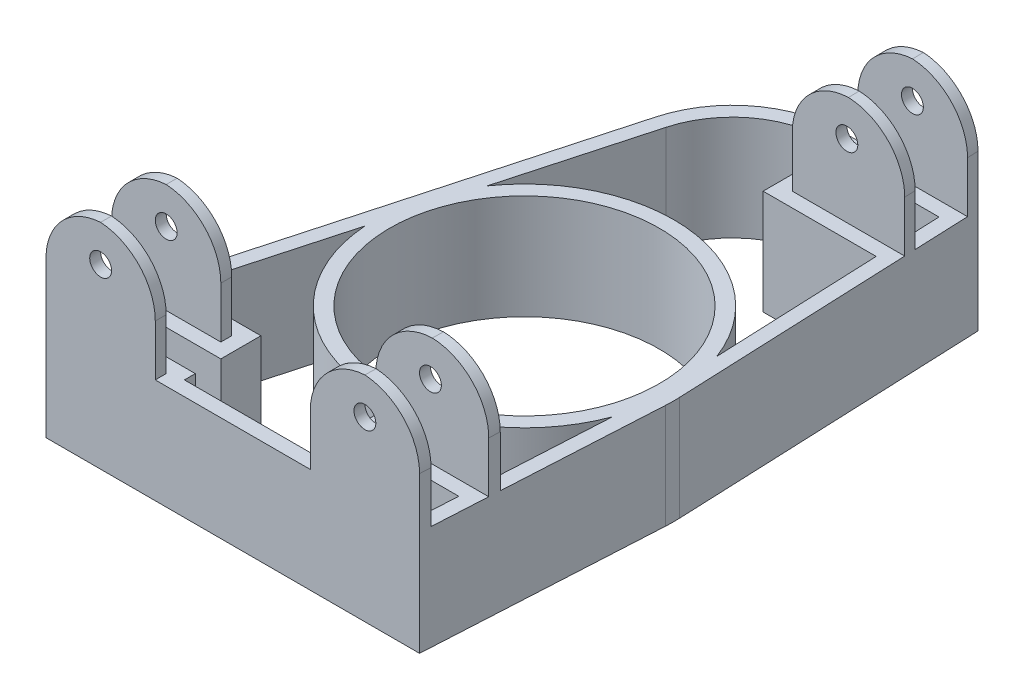
SolidWorks part; units mm, degrees
ref_plane "Front Plane" through (0, 0, 0) normal (0, 0, 1) x (1, 0, 0)
ref_plane "Top Plane" through (0, 0, 0) normal (0, 1, 0) x (1, 0, 0)
ref_plane "Right Plane" through (0, 0, 0) normal (1, 0, 0) x (0, 0, -1)
sketch "Sketch1" plane through (0, 0, 0) normal (0, 1, 0) x (1, 0, 0)
  line L0 (-80.1293, -86.7158) -> (50.1253, -86.7158)
  line L1 (54.7506, -2.9754) -> (50.1253, 108.0147)
  line L2 (50.1253, 108.0147) -> (2.5753, 108.0147)
  line L3 (-34.1543, 80.0411) -> (-72.7763, -60.0458)
  line L4 (50.1253, 108.0147) -> (50.1253, -86.7158) construction
  line L5 (50.1253, -86.7158) -> (54.7506, -2.9754)
  line L6 (-80.1293, -86.7158) -> (-80.1293, -60.0458)
  line L7 (-80.1293, -60.0458) -> (-72.7763, -60.0458)
  circle A0 centre (0, 0) radius 47
  circle A2 centre (0, 0) radius 120.65
  arc A3 (2.5753, 108.0147) -> (-34.1543, 80.0411) centre (2.5753, 69.9147) ccw
  point P10 (0, -47)
  point P11 (47, 0)
  point P16 (-47, 0)
  dimension "D2" = 94
  dimension "D3" = 7.62
  dimension "D4" = 8.89
  dimension "D5" = 26.67
  dimension "D1" = 241.3
  dimension "D6" = 38.1
extrude "Base" add sketch "Sketch1" along normal blind 36.5 contours L2 L3 L0 L1 A0 | L1 L4 A0 L5
sketch "Sketch2" plane through (0, 36.5, 0) normal (0, 1, 0) x (1, 0, 0)
  line L0 (50.1253, 108.0147) -> (50.2841, 104.2047)
  line L1 (54.7506, -2.9754) -> (50.1253, 108.0147) construction
  line L2 (50.2841, 104.2047) -> (12.0253, 104.2047)
  line L3 (12.0253, 104.2047) -> (12.0253, 108.0147)
  line L4 (50.1253, 108.0147) -> (2.5753, 108.0147) construction
  line L5 (12.0253, 108.0147) -> (50.1253, 108.0147)
  line L6 (12.0253, -82.9058) -> (50.3357, -82.9058)
  line L7 (50.3357, -82.9058) -> (50.1253, -86.7158)
  line L8 (-80.1293, -86.7158) -> (50.1253, -86.7158) construction
  line L9 (50.1253, -86.7158) -> (12.0253, -86.7158)
  line L10 (12.0253, -86.7158) -> (12.0253, -82.9058)
  line L11 (12.0253, 108.0147) -> (12.0253, -86.7158) construction
  line L12 (50.1253, -86.7158) -> (54.7506, -2.9754) construction
  line L13 (12.0253, 85.1547) -> (12.0253, 81.3447)
  line L14 (12.0253, 81.3447) -> (51.2367, 81.3447)
  line L15 (51.2367, 81.3447) -> (51.0779, 85.1547)
  line L16 (51.0779, 85.1547) -> (12.0253, 85.1547)
  line L17 (-80.1293, -86.7158) -> (-80.1293, -60.0458) construction
  line L18 (12.0253, -60.0458) -> (51.5984, -60.0458)
  line L19 (12.0253, -60.0458) -> (12.0253, -63.8558)
  line L20 (12.0253, -63.8558) -> (51.3879, -63.8558)
  line L21 (51.5984, -60.0458) -> (51.3879, -63.8558)
  line L22 (-42.0293, -60.0458) -> (-80.1293, -60.0458)
  line L23 (-42.0293, -60.0458) -> (-42.0293, -63.8558)
  line L24 (-42.0293, -63.8558) -> (-80.1293, -63.8558)
  line L25 (-80.1293, -60.0458) -> (-80.1293, -63.8558)
  line L26 (-42.0293, -86.7158) -> (-42.0293, -60.0458) construction
  line L27 (-80.1293, -82.9058) -> (-42.0293, -82.9058)
  line L28 (-80.1293, -82.9058) -> (-80.1293, -86.7158)
  line L29 (-80.1293, -86.7158) -> (-42.0293, -86.7158)
  line L30 (-42.0293, -82.9058) -> (-42.0293, -86.7158)
  line L31 (-80.1293, -86.7158) -> (50.1253, -86.7158) construction
  dimension "D1" = 38.1
  dimension "D2" = 3.81
  dimension "D3" = 3.81
  dimension "D4" = 19.05
  dimension "D5" = 3.81
  dimension "D6" = 3.81
  dimension "D7" = 19.05
  dimension "D8" = 38.1
  dimension "D9" = 3.81
  dimension "D10" = 3.81
extrude "A-Arms" add sketch "Sketch2" along normal blind 38.1
fillet "Fillet a-arm tab f" radius 20.32 12 edges at (50.2305, 74.6, 84.8108) (51.4932, 74.6, 61.9508) (12.0253, 74.6, 84.8108) (12.0253, 74.6, 61.9508) (51.1573, 74.6, -83.2497) (50.2047, 74.6, -106.1097) (12.0253, 74.6, -83.2497) (12.0253, 74.6, -106.1097) (-80.1293, 74.6, 84.8108) (-42.0293, 74.6, 84.8108) (-42.0293, 74.6, 61.9508) (-80.1293, 74.6, 61.9508)
fillet "Fillet2" radius 50.8 1 edges at (54.7506, 18.25, 2.9754)
ref_plane "Plane1" through (0, 1, 0) normal (0, -1, 0) x (-1, 0, 0)
sketch "Sketch3" plane through (0, 1, 0) normal (0, -1, 0) x (-1, 0, 0)
  line L0 (42.0933, 51.2453) -> (51.7371, 53.9041)
  line L1 (34.1543, 80.0411) -> (72.7763, -60.0458) construction
  line L2 (62.2108, -21.7233) -> (72.1885, -18.9724)
  line L3 (54.0145, 33.5988) -> (63.3923, -0.4157)
  line L4 (42.0933, 51.2453) -> (62.2108, -21.7233)
  circle A0 centre (0, 0) radius 71.12
  circle A1 centre (53.7624, 46.5582) radius 3.937
  circle A2 centre (70.1632, -11.6265) radius 3.937
  arc A3 (56.852, 39.5926) -> (51.7371, 53.9041) centre (53.7624, 46.5582) ccw
  arc A4 (72.1885, -18.9724) -> (69.039, -4.0899) centre (70.1632, -11.6265) ccw
  arc A5 (63.3923, -0.4157) -> (69.039, -4.0899) centre (68.2896, 0.9345) ccw
  arc A6 (54.0145, 33.5988) -> (56.852, 39.5926) centre (58.9118, 34.949) cw
  dimension "D1" = 60.452
  dimension "D2" = 142.24
  dimension "D3" = 7.874
  dimension "D4" = 7.874
  dimension "D5" = 15.24
  dimension "D6" = 15.24
  dimension "D7" = 5.08
extrude "Boss-Extrude3" add sketch "Sketch3" against normal blind 10 contours L3 A6 A3 A0 A1 L0 L4 L2 A2 A4 A5 | A0 A3 L0 A1 | L2 A4 A0 A2
fillet "Fillet3" radius 12.7 2 edges at (-42.0933, 6, -51.2453) (-62.2108, 6, 21.7233)
sketch "Sketch6" plane through (0, 0, -108.0147) normal (0, 0, -1) x (-1, 0, 0)
  line L0 (-31.067, 74.5598) -> (-31.067, 40.2979) construction
  circle A1 centre (-31.067, 61.8598) radius 3.81
  dimension "D1" = 12.7
extrude "Tab Holes 1" cut sketch "Sketch6" against normal through all
sketch "Sketch7" plane through (0, 0, 60.0458) normal (0, 0, -1) x (-1, 0, 0)
  line L0 (61.0793, 74.5603) -> (61.0793, 49.1603) construction
  circle A0 centre (61.0793, 61.8603) radius 3.81
  dimension "D1" = 12.7
extrude "Tab Holes 2" cut sketch "Sketch7" against normal through all
sketch "Sketch8" plane through (0, 0, 0) normal (0, 1, 0) x (1, 0, 0)
  line L0 (-42.0293, -86.7158) -> (12.0253, -86.7158) construction
  line L1 (50.3357, -82.9058) -> (51.3879, -63.8558) construction
  line L2 (51.5984, -60.0458) -> (54.6149, -5.433) construction
  line L3 (54.6481, -0.5162) -> (51.2367, 81.3447) construction
  line L4 (51.0779, 85.1547) -> (50.2841, 104.2047) construction
  line L5 (12.0253, 108.0147) -> (2.5753, 108.0147) construction
  line L6 (-34.1543, 80.0411) -> (-72.7763, -60.0458) construction
  line L7 (-42.0293, -86.7158) -> (12.0253, -86.7158)
  line L8 (50.3357, -82.9058) -> (51.3879, -63.8558)
  line L9 (51.5984, -60.0458) -> (54.6149, -5.433)
  line L10 (54.6481, -0.5162) -> (51.2367, 81.3447)
  line L11 (51.0779, 85.1547) -> (50.2841, 104.2047)
  line L12 (12.0253, 108.0147) -> (2.5753, 108.0147)
  line L13 (-34.1543, 80.0411) -> (-72.7763, -60.0458)
  line L14 (12.0253, 108.0147) -> (12.0253, 104.2047)
  line L15 (12.0253, 104.2047) -> (50.2841, 104.2047)
  line L16 (51.0779, 85.1547) -> (12.0253, 85.1547)
  line L17 (31.5432, 85.1547) -> (12.0253, 85.1547) construction
  line L18 (51.0779, 85.1547) -> (12.0253, 85.1547) construction
  line L19 (12.0253, 85.1547) -> (12.0253, 81.3447)
  line L20 (12.0253, 81.3447) -> (51.2367, 81.3447) construction
  line L21 (12.0253, 81.3447) -> (51.2367, 81.3447)
  line L22 (51.5984, -60.0458) -> (12.0253, -60.0458)
  line L23 (12.0253, -60.0458) -> (12.0253, -63.8558)
  line L24 (12.0253, -63.8558) -> (51.3879, -63.8558)
  line L25 (50.3357, -82.9058) -> (12.0253, -82.9058)
  line L26 (12.0253, -82.9058) -> (12.0253, -86.7158)
  line L28 (-42.0293, -60.0458) -> (-72.7763, -60.0458)
  line L29 (-42.0293, -60.0458) -> (-42.0293, -63.8558)
  line L30 (-61.0793, -63.8558) -> (-42.0293, -63.8558) construction
  line L31 (-80.1293, -63.8558) -> (-42.0293, -63.8558) construction
  line L32 (-42.0293, -63.8558) -> (-80.1293, -63.8558)
  line L33 (-80.1293, -63.8558) -> (-80.1293, -82.9058)
  line L34 (-80.1293, -82.9058) -> (-42.0293, -82.9058)
  line L35 (-42.0293, -82.9058) -> (-80.1293, -82.9058) construction
  line L36 (-42.0293, -82.9058) -> (-61.0793, -82.9058) construction
  line L37 (-42.0293, -82.9058) -> (-42.0293, -86.7158)
  line L38 (-36.9493, -77.8258) -> (-36.9493, -81.6358)
  line L39 (-36.9493, -81.6358) -> (6.9453, -81.6358)
  line L40 (6.9453, -77.8258) -> (6.9453, -81.6358)
  line L41 (45.5286, -77.8258) -> (6.9453, -77.8258)
  line L42 (45.5286, -77.8258) -> (46.0196, -68.9358)
  line L43 (6.9453, -68.9358) -> (46.0196, -68.9358)
  line L44 (6.9453, -54.9658) -> (6.9453, -68.9358)
  line L45 (46.7912, -54.9658) -> (6.9453, -54.9658)
  line L46 (46.7912, -54.9658) -> (49.5426, -5.1528)
  line L47 (49.5725, -0.7277) -> (46.364, 76.2647)
  line L48 (6.9453, 76.2647) -> (46.364, 76.2647)
  line L49 (6.9453, 90.2347) -> (6.9453, 76.2647)
  line L50 (45.7818, 90.2347) -> (6.9453, 90.2347)
  line L51 (45.7818, 90.2347) -> (45.4114, 99.1247)
  line L52 (6.9453, 99.1247) -> (45.4114, 99.1247)
  line L53 (6.9453, 102.9347) -> (6.9453, 99.1247)
  line L54 (6.9453, 102.9347) -> (2.5753, 102.9347)
  line L55 (-29.257, 78.6909) -> (-66.1062, -54.9658)
  line L56 (-36.9493, -54.9658) -> (-66.1062, -54.9658)
  line L57 (-36.9493, -54.9658) -> (-36.9493, -68.9358)
  line L58 (-36.9493, -68.9358) -> (-75.0493, -68.9358)
  line L59 (-75.0493, -68.9358) -> (-75.0493, -77.8258)
  line L60 (-75.0493, -77.8258) -> (-36.9493, -77.8258)
  arc A0 (54.6149, -5.433) -> (54.6481, -0.5162) centre (3.8922, -2.6314) ccw construction
  arc A1 (2.5753, 108.0147) -> (-34.1543, 80.0411) centre (2.5753, 69.9147) ccw construction
  arc A2 (54.6149, -5.433) -> (54.6481, -0.5162) centre (3.8922, -2.6314) ccw
  arc A3 (2.5753, 108.0147) -> (-34.1543, 80.0411) centre (2.5753, 69.9147) ccw
  circle A4 centre (0, 0) radius 47 construction
  circle A5 centre (0, 0) radius 47
  arc A6 (49.5426, -5.1528) -> (49.5725, -0.7277) centre (3.8922, -2.6314) ccw
  arc A7 (2.5753, 102.9347) -> (-29.257, 78.6909) centre (2.5753, 69.9147) ccw
  circle A9 centre (0, 0) radius 52.08
  dimension "D2" = 5.08
  dimension "D1" = 5.08
extrude "Cut-Extrude2" cut sketch "Sketch8" along normal through all contours L47 A9 L55 A7 L54 L53 L52 L51 L50 L49 L48 | L55 A9 L46 L45 L44 L43 L42 L41 L40 L39 L38 L60 L59 L58 L57 L56
